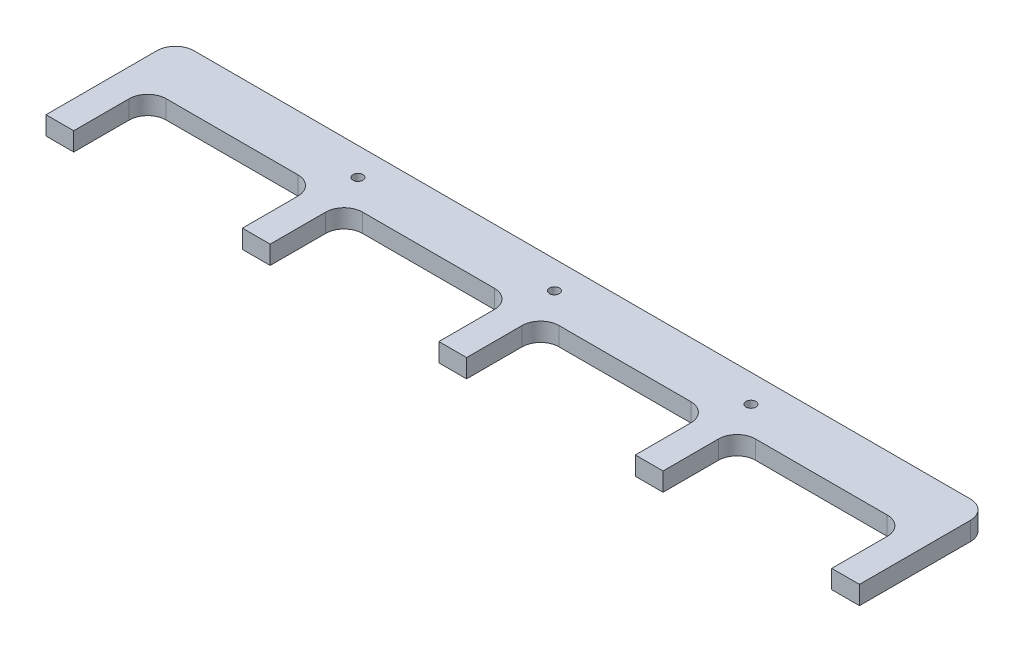
SolidWorks part; units mm, degrees
material "Acrylic (Medium-high impact)"
ref_plane "Front Plane" through (0, 0, 0) normal (0, 0, 1) x (1, 0, 0)
ref_plane "Top Plane" through (0, 0, 0) normal (0, 1, 0) x (1, 0, 0)
ref_plane "Right Plane" through (0, 0, 0) normal (1, 0, 0) x (0, 0, -1)
sketch "Sketch1" plane through (0, 0, 0) normal (0, 1, 0) x (1, 0, 0)
  line L0 (0, 0) -> (0, 88.9) construction
  line L1 (139.7, 88.9) -> (-139.7, 88.9) construction
  line L2 (139.7, 88.9) -> (139.7, -88.9) construction
  line L3 (139.7, -88.9) -> (-139.7, -88.9) construction
  line L4 (-139.7, 88.9) -> (-139.7, -88.9) construction
  line L5 (0, 0) -> (139.7, 0) construction
  line L6 (-139.7, 82.55) -> (-139.7, 44.45)
  line L7 (-139.7, 44.45) -> (-130.175, 44.45)
  line L8 (-130.175, 44.45) -> (-130.175, 63.5)
  line L9 (-123.825, 69.85) -> (-78.5812, 69.85)
  line L10 (-72.2312, 63.5) -> (-72.2313, 44.45)
  line L11 (-72.2313, 44.45) -> (-62.7062, 44.45)
  line L12 (-62.7062, 44.45) -> (-62.7062, 63.5)
  line L13 (-56.3562, 69.85) -> (-11.1125, 69.85)
  line L14 (-4.7625, 63.5) -> (-4.7625, 44.45)
  line L15 (-4.7625, 44.45) -> (4.7625, 44.45)
  line L16 (4.7625, 44.45) -> (4.7625, 63.5)
  line L17 (11.1125, 69.85) -> (56.3562, 69.85)
  line L18 (130.175, 63.5) -> (130.175, 44.45)
  line L19 (130.175, 44.45) -> (139.7, 44.45)
  line L20 (139.7, 44.45) -> (139.7, 82.55)
  line L21 (133.35, 88.9) -> (-133.35, 88.9)
  line L22 (62.7062, 63.5) -> (62.7062, 44.45)
  line L23 (62.7062, 44.45) -> (72.2313, 44.45)
  line L24 (72.2313, 44.45) -> (72.2313, 63.5)
  line L25 (78.5813, 69.85) -> (123.825, 69.85)
  line L26 (0, 44.45) -> (0, 69.85) construction
  line L27 (-133.35, 82.55) -> (-133.35, 88.9) construction
  line L28 (0, 0) -> (-82.1531, 0) construction
  line L29 (-120.2531, 63.5) -> (-82.1531, 63.5) construction
  line L30 (-120.2531, 63.5) -> (-120.2531, -63.5) construction
  line L31 (-120.2531, -63.5) -> (-82.1531, -63.5) construction
  line L32 (-82.1531, 63.5) -> (-82.1531, -63.5) construction
  line L33 (-101.2031, 63.5) -> (-101.2031, 69.85) construction
  line L34 (-120.2531, 63.5) -> (-130.175, 63.5) construction
  line L35 (139.7, 79.375) -> (-139.7, 79.375) construction
  line L36 (-33.7344, 69.85) -> (-33.7344, 79.375) construction
  line L37 (-33.7344, 79.375) -> (-33.7344, 88.9) construction
  line L38 (-67.4688, 44.45) -> (-67.4688, 79.375) construction
  line L39 (0, 44.45) -> (0, 79.375) construction
  line L40 (67.4688, 44.45) -> (67.4688, 79.375) construction
  arc A0 (123.825, 69.85) -> (130.175, 63.5) centre (123.825, 63.5) cw
  arc A1 (133.35, 88.9) -> (139.7, 82.55) centre (133.35, 82.55) cw
  arc A2 (-133.35, 88.9) -> (-139.7, 82.55) centre (-133.35, 82.55) ccw
  arc A3 (78.5813, 69.85) -> (72.2313, 63.5) centre (78.5813, 63.5) ccw
  arc A4 (56.3562, 69.85) -> (62.7062, 63.5) centre (56.3562, 63.5) cw
  arc A5 (11.1125, 69.85) -> (4.7625, 63.5) centre (11.1125, 63.5) ccw
  arc A6 (-11.1125, 69.85) -> (-4.7625, 63.5) centre (-11.1125, 63.5) cw
  arc A7 (-56.3562, 69.85) -> (-62.7062, 63.5) centre (-56.3562, 63.5) ccw
  arc A8 (-78.5812, 69.85) -> (-72.2312, 63.5) centre (-78.5812, 63.5) cw
  arc A9 (-123.825, 69.85) -> (-130.175, 63.5) centre (-123.825, 63.5) ccw
  circle A10 centre (-67.4688, 79.375) radius 1.7
  circle A11 centre (0, 79.375) radius 1.7
  circle A12 centre (67.4688, 79.375) radius 1.7
  point P0 (0, 0)
  point P58 (-72.2312, 69.85)
  point P61 (-130.175, 69.85)
  dimension "D8" = 6.35
  dimension "D10" = 3.4
  dimension "D1" = 6.35
  dimension "D2" = 279.4
  dimension "D3" = 9.525
  dimension "D4" = 45.2437
  dimension "D5" = 19.05
  dimension "D6" = 38.1
  dimension "D7" = 127
  dimension "D9" = 44.45
  dimension "D11" = 19.05
extrude "Boss-Extrude1" add sketch "Sketch1" along normal blind 6.35
equation "\"D11@Sketch1\"=\"D5@Sketch1\""
